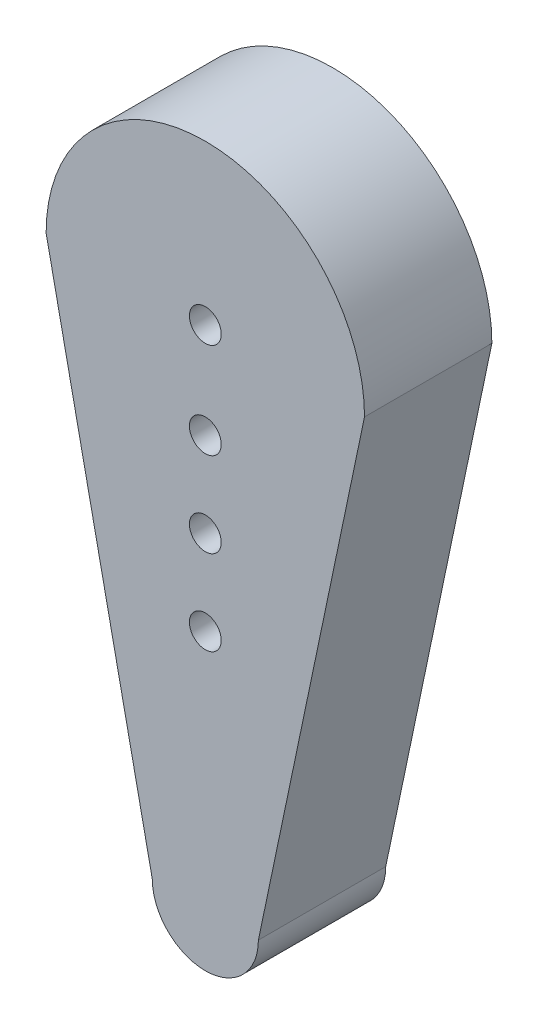
SolidWorks part; units mm, degrees
ref_plane "Front Plane" through (0, 0, 0) normal (0, 0, 1) x (1, 0, 0)
ref_plane "Top Plane" through (0, 0, 0) normal (0, 1, 0) x (1, 0, 0)
ref_plane "Right Plane" through (0, 0, 0) normal (1, 0, 0) x (0, 0, -1)
sketch "Sketch2" plane through (0, 0, 0) normal (0, 0, 1) x (1, 0, 0)
  line L0 (0, -20.6761) -> (0, 20.6761) construction
  line L1 (-7.5, 0) -> (-2.5, -23.85)
  line L2 (7.5, 0) -> (2.5, -23.85)
  arc A0 (7.5, 0) -> (-7.5, 0) centre (0, 0) ccw
  arc A1 (-2.5, -23.85) -> (2.5, -23.85) centre (0, -23.85) ccw
  dimension "D1" = 15
  dimension "D2" = 5
  dimension "D3" = 26.35
extrude "Boss-Extrude1" add sketch "Sketch2" along normal blind 6
sketch "Sketch3" plane through (0, 0, 0) normal (0, 0, 1) x (1, 0, 0)
  line L0 (-3.75, 0) -> (-2.25, -15)
  line L1 (2.25, -15) -> (3.75, 0)
  line L2 (0, -1.65) -> (0, 1.65) construction
  arc A0 (3.75, 0) -> (-3.75, 0) centre (0, 0) ccw
  arc A1 (-2.25, -15) -> (2.25, -15) centre (0, -15) ccw
  point P8 (0, 0)
  point P9 (0, 0)
  dimension "D1" = 7.5
  dimension "D2" = 4.5
  dimension "D3" = 15
extrude "Cut-Extrude3" cut sketch "Sketch3" along normal blind 4.7
sketch "Sketch4" plane through (0, 0, 4.7) normal (0, 0, -1) x (-1, 0, 0)
  circle A0 centre (0, 0) radius 0.75
  point P2 (0, 0)
  dimension "D1" = 1.5
extrude "Cut-Extrude4" cut sketch "Sketch4" against normal through all both and the other way through all
sketch "Sketch6" plane through (0, 0, 4.7) normal (0, 0, -1) x (-1, 0, 0)
  line L0 (0, 3.3) -> (0, -3.3) construction
  line L1 (3.3, 0) -> (-3.3, 0) construction
  circle A0 centre (0, -4.5) radius 0.75
  point P2 (0, 0)
  dimension "D1" = 1.5
  dimension "D2" = 4.5
extrude "Cut-Extrude6" cut sketch "Sketch6" against normal through all both and the other way through all
pattern_linear "LPattern1" count 3 spacing 4 along (0, -1, 0) of "Cut-Extrude6"
